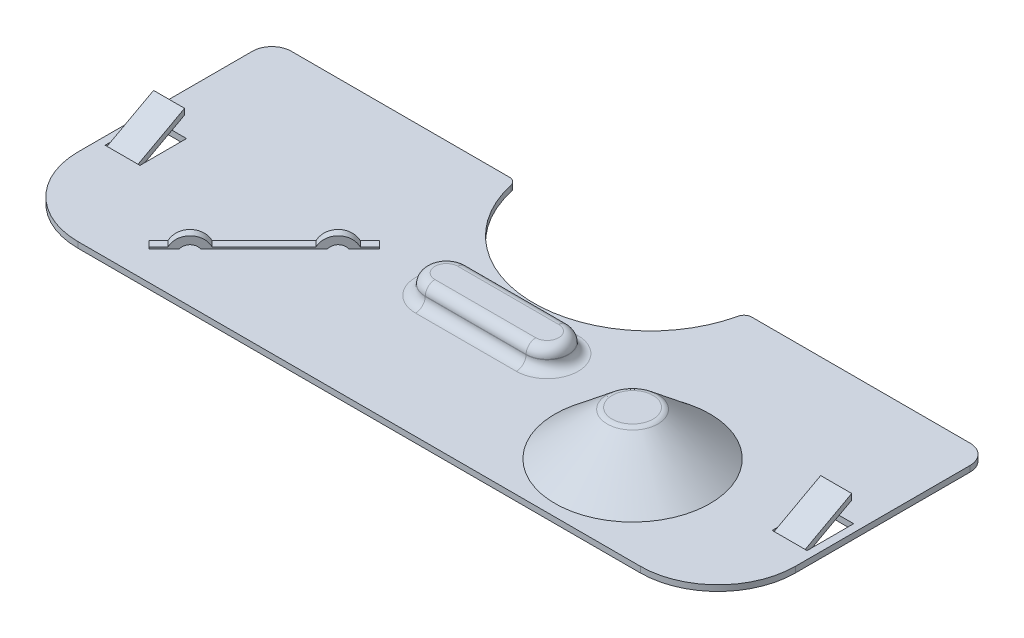
SolidWorks part; units mm, degrees
note: '?' marks a value the reader was unsure of.
material "Plain Carbon Steel"
ref_plane "Front Plane" through (0, 0, 0) normal (0, 0, 1) x (1, 0, 0)
ref_plane "Top Plane" through (0, 0, 0) normal (0, 1, 0) x (1, 0, 0)
ref_plane "Right Plane" through (0, 0, 0) normal (1, 0, 0) x (0, 0, -1)
sketch "Sketch1" plane through (0, 0, 0) normal (0, 1, 0) x (1, 0, 0)
  line L1 (-18.5, 7) -> (18.5, 7)
  line L2 (-18.5, 7) -> (-18.5, -7)
  line L3 (-18.5, -7) -> (18.5, -7)
  line L4 (18.5, 7) -> (18.5, -7)
  line L5 (-18.5, 7) -> (18.5, -7) construction
  line L6 (-18.5, -7) -> (18.5, 7) construction
  point P0 (0, 0)
  dimension "D1" = 37
  dimension "D2" = 14
extrude "BASE" add sketch "Sketch1" along normal blind 0.3
sketch "Sketch3" plane through (0, 0.3, 0) normal (0, 1, 0) x (1, 0, 0)
  line L1 (0, 2) -> (0, 7) construction
  line L2 (18.5, 7) -> (-18.5, 7) construction
  circle A0 centre (0, 8) radius 6
  dimension "D1" = 12
  dimension "D2" = 5
extrude "TOP SEMI CIRCLE" cut sketch "Sketch3" against normal through all
sketch "Sketch2" plane through (0, 0.3, 0) normal (0, 1, 0) x (1, 0, 0)
  line L0 (0, -2.4) -> (9.5, -2.4) construction
  line L1 (0, -7) -> (0, -2.4) construction
  line L2 (-18.5, -7) -> (18.5, -7) construction
  line L3 (9.5, -6.4) -> (9.5, -7) construction
  circle A0 centre (9.5, -2.4) radius 4
  dimension "D1" = 8
  dimension "D2" = 9.5
  dimension "D3" = 4.6
  dimension "D4" = 0.6
extrude "PT CUT" cut sketch "Sketch2" against normal through all
ref_axis "POSITIVE" through (9.5, 0, 2.4) along (0, 1, 0)
ref_plane "PT REFERENCE PLANE" through (0, 0, 2.4) normal (0, 0, 1) x (1, 0, 0)
sketch "Sketch4" plane through (0, 0, 2.4) normal (0, 0, 1) x (1, 0, 0)
  line L0 (9.5, 2.6) -> (10.5568, 2.6)
  line L2 (13.5, 0) -> (13.2, 0)
  line L4 (10.5936, 2.3) -> (9.5, 2.3)
  line L5 (9.5, 2.3) -> (9.5, 2.6)
  line L6 (5.5, 0) -> (13.5, 0) construction
  line L7 (13.5, 0) -> (13.5, 0.3) construction
  line L8 (10.8107, 2.5091) -> (13.5, 0.3)
  line L9 (13.5, 0.3) -> (5.5, 0.3) construction
  line L10 (13.5, 0) -> (13.5, 0.3)
  line L11 (9.5, 0) -> (9.5, 0.3) construction
  line L12 (13.1, 0.1) -> (13.1, 0.2527)
  line L13 (13.0635, 0.33) -> (10.7206, 2.2545)
  line L14 (-18.5, 0) -> (18.5, 0) construction
  line L15 (13.1, 0.3) -> (13.5, 0.3) construction
  arc A0 (10.5936, 2.3) -> (10.7206, 2.2545) centre (10.5936, 2.1) cw
  arc A1 (10.8107, 2.5091) -> (10.5568, 2.6) centre (10.5568, 2.2) ccw
  arc A2 (13.1, 0.1) -> (13.2, 0) centre (13.2, 0.1) ccw
  arc A3 (13.0635, 0.33) -> (13.1, 0.2527) centre (13, 0.2527) cw
  point P22 (10.7, 2.6)
  dimension "D4" = 0.2
  dimension "D5" = 0.4
  dimension "D6" = 0.1
  dimension "D7" = 0.1
  dimension "D1" = 0.3
  dimension "D2" = 1.2
  dimension "D3" = 2.6
revolve "POSITIVE TERMINAL" add sketch "Sketch4" angle 360 about axis through (9.5, 0, 2.4) along (0, 1, 0)
sketch "Sketch5" plane through (0, 0.3, 0) normal (0, 1, 0) x (1, 0, 0)
  line L0 (-2.6, 0.1) -> (2.6, 0.1) construction
  line L1 (-2.6, 1.2) -> (2.6, 1.2)
  line L2 (-2.6, -1) -> (2.6, -1)
  line L4 (-18.5, -7) -> (18.5, -7) construction
  line L5 (0, 0.1) -> (0, -7) construction
  arc A0 (-2.6, 1.2) -> (-2.6, -1) centre (-2.6, 0.1) ccw
  arc A1 (2.6, -1) -> (2.6, 1.2) centre (2.6, 0.1) ccw
  point P2 (0, 0.1)
  dimension "D1" = 5.2
  dimension "D2" = 2.2
  dimension "D3" = 6
extrude "MID SLOT BOSS" add sketch "Sketch5" along normal blind 1 draft 1
sketch "Sketch6" plane through (0, 0, 0) normal (0, -1, 0) x (1, 0, 0)
  line L0 (2.6, -0.1) -> (-2.6, -0.1) construction
  line L1 (2.6, -1) -> (-2.6, -1)
  line L2 (2.6, 0.8) -> (-2.6, 0.8)
  arc A0 (2.6, -1) -> (2.6, 0.8) centre (2.6, -0.1) ccw
  arc A1 (-2.6, 0.8) -> (-2.6, -1) centre (-2.6, -0.1) ccw
  arc A3 (2.6, -1.2) -> (2.6, 1) centre (2.6, -0.1) ccw construction
  point P2 (0, -0.1)
  dimension "D1" = 0.2
extrude "MSB CUT" cut sketch "Sketch6" against normal offset from surface 0.2 draft 1
sketch "Sketch7" plane through (0, 0.3, 0) normal (0, 1, 0) x (1, 0, 0)
  line L1 (18.1, -2) -> (16.3, -2)
  line L2 (18.1, -2) -> (18.1, 0.4)
  line L3 (18.1, 0.4) -> (16.3, 0.4)
  line L4 (16.3, -2) -> (16.3, 0.4)
  line L5 (18.1, -2) -> (16.3, 0.4) construction
  line L6 (18.1, 0.4) -> (16.3, -2) construction
  line L7 (-18.5, -7) -> (18.5, -7) construction
  line L8 (18.5, -7) -> (18.5, 7) construction
  dimension "D1" = 1.8
  dimension "D2" = 0.4
  dimension "D3" = 5
  dimension "D4" = 2.4
extrude "LOCKING CLAMP CUT" cut sketch "Sketch7" against normal through all
ref_plane "LCC REFERENCE PLANE" through (17.2, 0, 0) normal (-1, 0, 0) x (0, 0, 1)
sketch "Sketch9" plane through (17.2, 0, 0) normal (-1, 0, 0) x (0, 0, 1)
  line L0 (2, 0.3) -> (-0.4, 1.6)
  line L1 (-0.4, 1.6) -> (-0.4, 1.3)
  line L2 (-0.4, 1.3) -> (2, 0)
  line L3 (2, 0) -> (2, 0.3)
  line L5 (-7, 0) -> (7, 0) construction
  line L6 (-0.4, 0) -> (-0.4, 0.3) construction
  dimension "D1" = 1.6
extrude "LOCKING CLAMP" add sketch "Sketch9" along normal mid plane 1.6
mirror "LC M" about plane through (0, 0, 0) normal (1, 0, 0) of "LOCKING CLAMP CUT", "LOCKING CLAMP"
sketch "SC RP SKETCH" plane through (0, 0, 0) normal (0, 1, 0) x (1, 0, 0)
  line L0 (-6.5302, 0.5698) -> (-12.4698, -5.3698) construction
  line L1 (9.5, -2.4) -> (-9.5, -2.4) construction
  line L2 (0, 0) -> (0, -2.4) construction
  dimension "D1" = 8.4
  dimension "D2" = 45
ref_plane "SC RP" through (-3.55, 0, -3.55) normal (-0.7071, 0, -0.7071) x (-0.7071, 0, 0.7071)
ref_axis "NEGATIVE" through (-9.5, 0, 2.4) along (0, 1, 0)?
sketch "Sketch11" plane through (-3.55, 0, -3.55) normal (-0.7071, 0, -0.7071) x (-0.7071, 0, 0.7071)
  line L0 (11.1146, 0) -> (5.7146, 0) construction
  line L1 (12.6146, 0) -> (11.7062, 0)
  line L2 (10.523, 0) -> (6.3062, 0)
  line L3 (4.2146, 0) -> (5.123, 0)
  arc A0 (11.6076, 0.0833) -> (10.6216, 0.0833) centre (11.1146, 0) ccw
  arc A1 (6.2076, 0.0833) -> (5.2216, 0.0833) centre (5.7146, 0) ccw
  arc A2 (5.123, 0) -> (5.2216, 0.0833) centre (5.123, 0.1) ccw
  arc A3 (6.2076, 0.0833) -> (6.3062, 0) centre (6.3062, 0.1) ccw
  arc A4 (10.523, 0) -> (10.6216, 0.0833) centre (10.523, 0.1) ccw
  arc A5 (11.7062, 0) -> (11.6076, 0.0833) centre (11.7062, 0.1) cw
  point P13 (5.2146, 0)
  point P16 (6.2146, 0)
  point P19 (10.6146, 0)
  point P22 (11.6146, 0)
  dimension "D2" = 1
  dimension "D3" = 0.1
  dimension "D1" = 5.4
extrude "SPRING CLASP" add sketch "Sketch11" along normal mid plane 0.4 thin
fillet "TS F" radius 1 2 edges at (-18.5, 0.15, -7) (18.5, 0.15, -7)
fillet "BS F" radius 4 2 edges at (18.5, 0.15, 7) (-18.5, 0.15, 7)
fillet "SC F" radius 0.4 2 edges at (-5.9161, 0.15, -7) (5.9161, 0.15, -7)
fillet "MSB OUTER" radius 0.5 8 edges at (-3.6825, 1.3, -0.1) (0, 1.3, -1.1825) (3.6825, 1.3, -0.1) (-3.7, 0.3, -0.1) (0, 0.3, -1.2) (3.7, 0.3, -0.1) (0, 1.3, 0.9825) (0, 0.3, 1)
fillet "MSB INNER" radius 0.5 8 edges at (-3.5, 0, -0.1) (0, 0, 0.8) (3.5, 0, -0.1) (-3.4808, 1.1, -0.1) (0, 1.1, 0.7808) (3.4808, 1.1, -0.1) (0, 0, -1) (0, 1.1, -0.9808)
